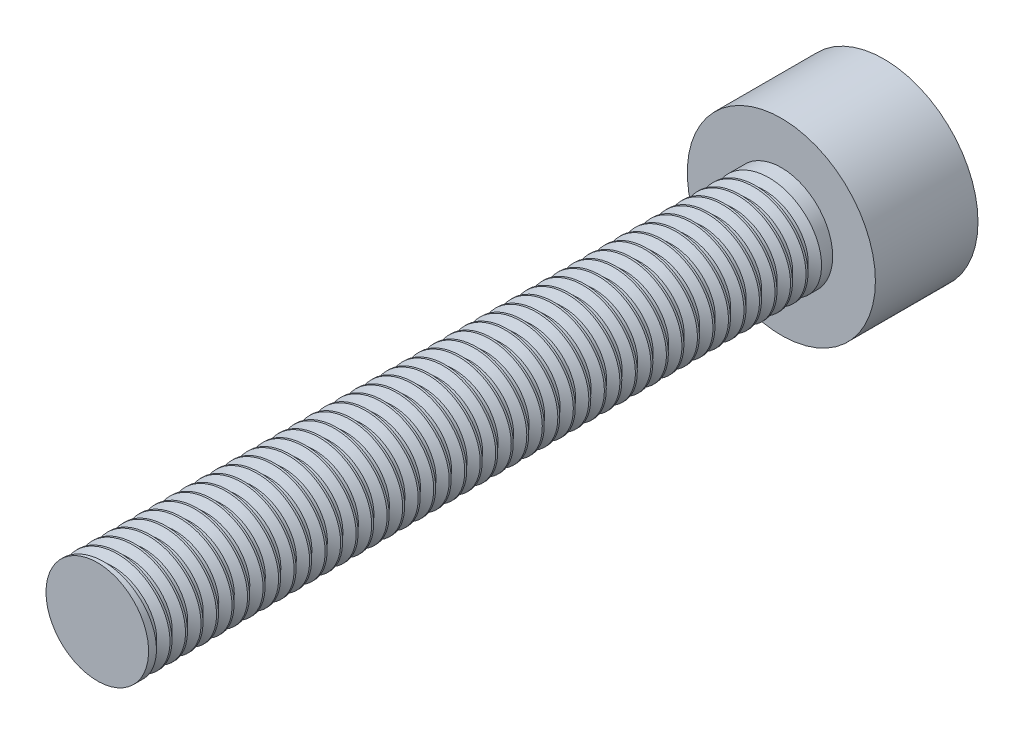
SolidWorks part; units mm, degrees
ref_plane "前视基准面" through (0, 0, 0) normal (0, 0, 1) x (1, 0, 0)
ref_plane "上视基准面" through (0, 0, 0) normal (0, 1, 0) x (1, 0, 0)
ref_plane "右视基准面" through (0, 0, 0) normal (1, 0, 0) x (0, 0, -1)
sketch "草图1" plane through (0, 0, 0) normal (0, 0, 1) x (1, 0, 0)
  circle A0 centre (0, 0) radius 2.75
  dimension "D1" = 5.5
extrude "凸台-拉伸1" add sketch "草图1" along normal blind 3
sketch "草图2" plane through (0, 0, 3) normal (0, 0, 1) x (1, 0, 0)
  circle A0 centre (0, 0) radius 1.5
  dimension "D1" = 3
extrude "凸台-拉伸2" add sketch "草图2" along normal blind 20
sketch "草图3" plane through (0, 0, 0) normal (0, 0, -1) x (-1, 0, 0)
  line L1 (1.1762, -1.2714) -> (1.6892, 0.3829)
  line L2 (1.6892, 0.3829) -> (0.513, 1.6543)
  line L3 (0.513, 1.6543) -> (-1.1762, 1.2714)
  line L4 (-1.1762, 1.2714) -> (-1.6892, -0.3829)
  line L5 (-1.6892, -0.3829) -> (-0.513, -1.6543)
  line L6 (-0.513, -1.6543) -> (1.1762, -1.2714)
  circle A0 centre (0, 0) radius 1.5 construction
  dimension "D1" = 3
extrude "切除-拉伸1" cut sketch "草图3" against normal blind 1.5
thread "螺纹线1" pitch 0.4536 method cut profile "螺纹线轮廓1" start angle 0, offset 0, length 19.5, pitch 0.4536, diameter 3
ref_plane "基准面4" through (-1.5, 0, 23) normal (0, -1, 0) x (-1, 0, 0)
sketch "螺纹线轮廓1" plane through (-1.5, 0, 23) normal (0, -1, 0) x (-1, 0, 0)
  line L0 (0, 0) -> (0, 0.4536) construction
  line L11 (0, 0) -> (0, 0.3969)
  line L12 (0, 0.3969) -> (-0.2455, 0.2551)
  line L13 (-0.2455, 0.2551) -> (-0.2455, 0.1417)
  line L15 (-0.2455, 0.1417) -> (0, 0)
  line L17 (-0.2455, 0.1984) -> (0, 0.1984) construction
  point P2 (0, 0)
  dimension "Pitch" = 0.4536
  dimension "Profile_Angle" = 60
  dimension "Profile_Land" = 0.1134
  dimension "Profile_Height" = 0.2455
